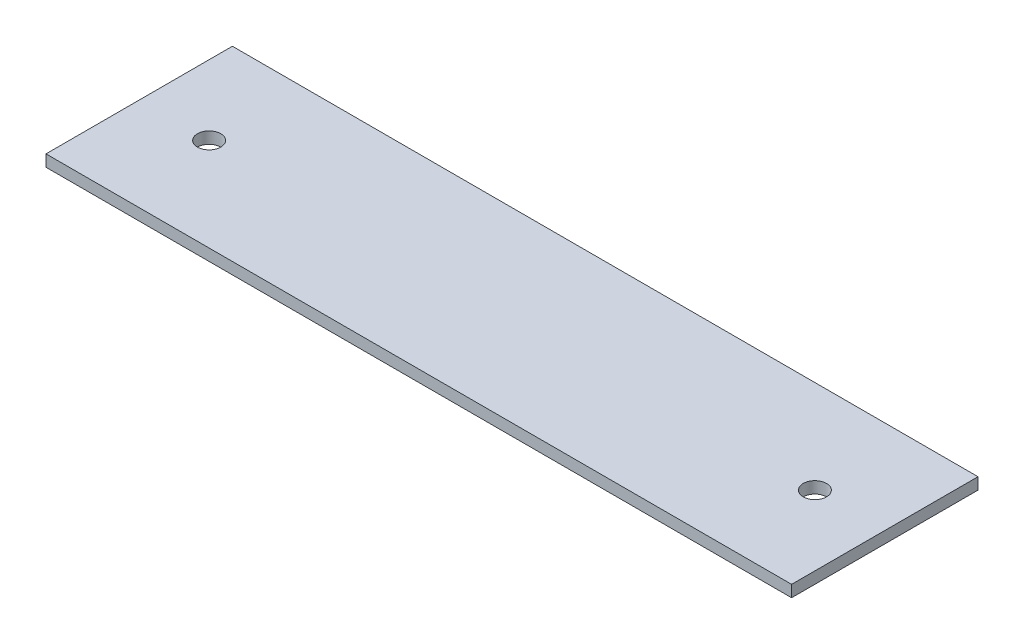
SolidWorks part; units mm, degrees
ref_plane "Front Plane" through (0, 0, 0) normal (0, 0, 1) x (1, 0, 0)
ref_plane "Top Plane" through (0, 0, 0) normal (0, 1, 0) x (1, 0, 0)
ref_plane "Right Plane" through (0, 0, 0) normal (1, 0, 0) x (0, 0, -1)
sketch "Sketch1" plane through (0, 0, 0) normal (0, 1, 0) x (1, 0, 0)
  line L1 (0, 0) -> (203.2, 0)
  line L2 (0, 0) -> (0, 50.8)
  line L3 (0, 50.8) -> (203.2, 50.8)
  line L4 (203.2, 0) -> (203.2, 50.8)
  dimension "D1" = 203.2
  dimension "D2" = 50.8
extrude "Boss-Extrude1" add sketch "Sketch1" along normal blind 3.175
sketch "Sketch2" plane through (0, 0, 0) normal (0, -1, 0) x (-1, 0, 0)
  line L0 (-203.2, 0) -> (-203.2, 50.8) construction
  line L1 (0, 0) -> (-203.2, 0) construction
  circle A0 centre (-184.15, 25.4) radius 3.175
  circle A1 centre (-19.05, 25.4) radius 3.175
  dimension "D1" = 19.05
  dimension "D2" = 25.4
  dimension "D3" = 25.4
  dimension "D4" = 184.15
extrude "Cut-Extrude1" cut sketch "Sketch2" against normal blind 24.638
